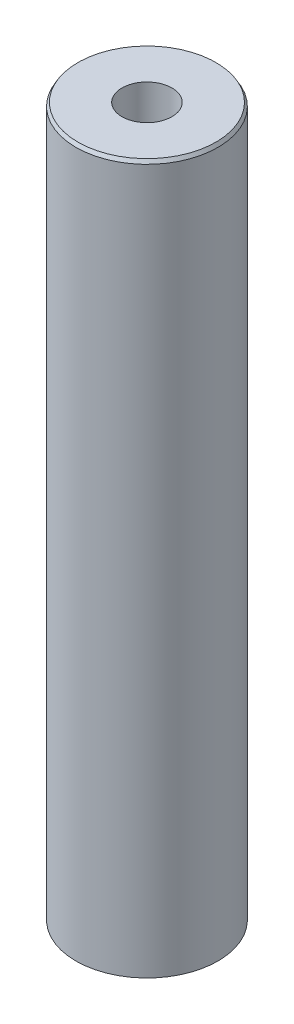
SolidWorks part; units mm, degrees
ref_plane "Front Plane" through (0, 0, 0) normal (0, 0, 1) x (1, 0, 0)
ref_plane "Top Plane" through (0, 0, 0) normal (0, 1, 0) x (1, 0, 0)
ref_plane "Right Plane" through (0, 0, 0) normal (1, 0, 0) x (0, 0, -1)
sketch "Sketch1" plane through (0, 0, 0) normal (0, 1, 0) x (1, 0, 0)
  circle A0 centre (0, 0) radius 60
  dimension "SHAFT_OD" = 120
extrude "Boss-Extrude1" add sketch "Sketch1" along normal blind 600
sketch "Sketch2" plane through (0, 0, 0) normal (0, 1, 0) x (1, 0, 0)
  circle A0 centre (0, 0) radius 21.0891
  dimension "BORE_D" = 42.1783
extrude "Cut-Extrude1" cut sketch "Sketch2" along normal through all
chamfer "Chamfer1" distance 2.9656 angle 30 2 edges at (0, 600, 60) (0, 0, 60) first distance on face at (0, 600, 60) first distance on face at (0, 0, 21.0891)
